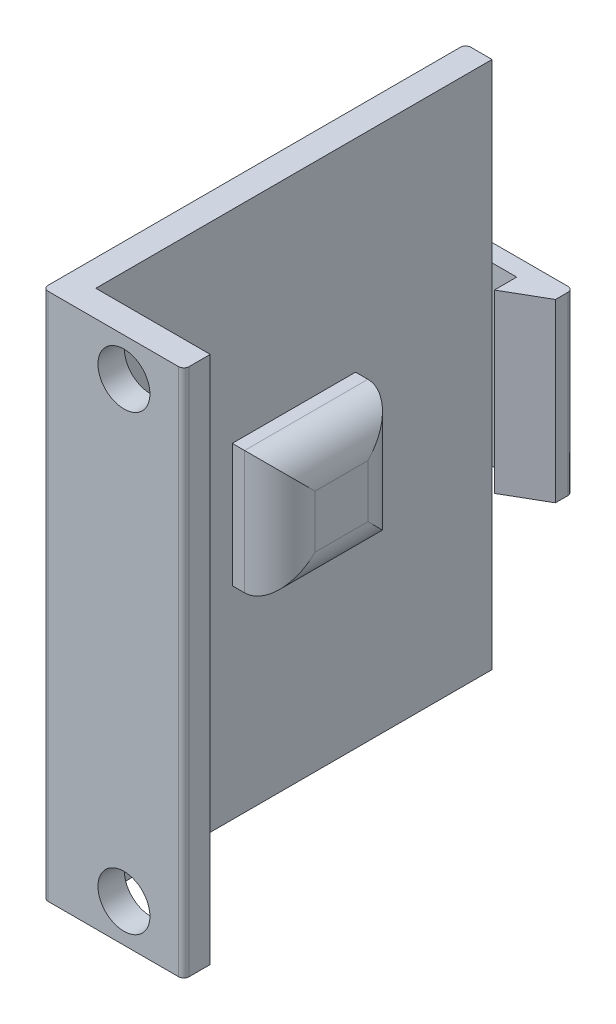
SolidWorks part; units mm, degrees
ref_plane "Front Plane" through (0, 0, 0) normal (0, 0, 1) x (1, 0, 0)
ref_plane "Top Plane" through (0, 0, 0) normal (0, 1, 0) x (1, 0, 0)
ref_plane "Right Plane" through (0, 0, 0) normal (1, 0, 0) x (0, 0, -1)
sketch "Sketch1" plane through (0, 0, 0) normal (0, 1, 0) x (1, 0, 0)
  line L0 (0, 0) -> (-2.2, 0)
  line L5 (-2.2, 0) -> (-2.2, -1.2702)
  line L6 (-2.2, -1.2702) -> (0, 0)
  dimension "D1" = 60
  dimension "D2" = 2.2
extrude "Boss-Extrude1" add sketch "Sketch1" along normal blind 5 and the other way blind 5
sketch "Sketch2" plane through (0, 0, 0) normal (0, 0, -1) x (-1, 0, 0)
  line L0 (0, 5) -> (2.2, 5) construction
  line L1 (0, -5) -> (3.6, -5)
  line L2 (0, -5) -> (0, 5)
  line L3 (0, 5) -> (3.6, 5)
  line L4 (3.6, -5) -> (3.6, 5)
  line L5 (0, -5) -> (3.6, 5) construction
  line L6 (0, 5) -> (3.6, -5) construction
  line L7 (2.2, -5) -> (2.2, 5) construction
  point P4 (1.8, 0)
  dimension "D1" = 1.4
extrude "Boss-Extrude2" add sketch "Sketch2" along normal blind 1
sketch "Sketch3" plane through (-3.6, 0, 0) normal (-1, 0, 0) x (0, 0, 1)
  line L0 (0, 0) -> (12.5427, 0) construction
  line L1 (0, -15) -> (22.5, -15)
  line L2 (0, -15) -> (0, 15)
  line L3 (0, 15) -> (22.5, 15)
  line L4 (22.5, -15) -> (22.5, 15)
  line L5 (0, -15) -> (22.5, 15) construction
  line L6 (0, 15) -> (22.5, -15) construction
  line L7 (0, -5) -> (0, 5) construction
  line L9 (0, 5) -> (-1, 5)
  line L10 (0, 5) -> (0, -5)
  line L11 (0, -5) -> (-1, -5)
  line L12 (-1, 5) -> (-1, -5)
  line L13 (0, 5) -> (-1, -5) construction
  line L14 (0, -5) -> (-1, 5) construction
  point P4 (11.25, 0)
  point P16 (-0.5, 0)
  line M6 (0, -5) -> (0, 5)
  line M7 (0, 5) -> (-1, 5)
  line M8 (-1, 5) -> (-1, -5)
  line M9 (-1, -5) -> (0, -5)
  dimension "D1" = 22.5
  dimension "D2" = 30
extrude "Boss-Extrude3" add sketch "Sketch3" along normal blind 1.5 contours L1 L4 L3 L2 M6 | M9 M6 M7 M8 region at (-3.6, 0, 11.25) region at (-3.6, 0, -0.5)
sketch "Sketch4" plane through (0, 0, 22.5) normal (0, 0, 1) x (1, 0, 0)
  line L0 (-4.35, 0) -> (3.106, 0) construction
  line L1 (-5.1, -15) -> (-3.6, -15)
  line L2 (-5.1, -15) -> (-5.1, 15)
  line L3 (-5.1, 15) -> (-3.6, 15)
  line L4 (-3.6, -15) -> (-3.6, 15)
  line L5 (-5.1, -15) -> (-3.6, 15) construction
  line L6 (-5.1, 15) -> (-3.6, -15) construction
  line L7 (-3.6, -15) -> (2.9, -15)
  line L8 (-3.6, -15) -> (-3.6, 15)
  line L9 (-3.6, 15) -> (2.9, 15)
  line L10 (2.9, -15) -> (2.9, 15)
  line L11 (-3.6, -15) -> (2.9, 15) construction
  line L12 (-3.6, 15) -> (2.9, -15) construction
  circle A0 centre (-0.5, 12.84) radius 1.475
  circle A1 centre (-0.5, -12.84) radius 1.475
  point P4 (-4.35, 0)
  point P11 (-0.35, 0)
  line M5 (-3.6, -15) -> (-3.6, 15)
  line M6 (-3.6, 15) -> (-5.1, 15)
  line M7 (-5.1, 15) -> (-5.1, -15)
  line M8 (-5.1, -15) -> (-3.6, -15)
  dimension "D4" = 2.95
  dimension "D1" = 30
  dimension "D2" = 6.5
  dimension "D3" = 3.4
  dimension "D5" = 2.16
extrude "Boss-Extrude4" add sketch "Sketch4" along normal blind 1.5 contours L7 L10 L9 M5 | M8 M5 M6 M7 region at (-4.35, 0, 22.5) region at (-0.3387, 0, 22.5)
ref_plane "Plane1" through (0, 0, 0) normal (0, 1, 0) x (1, 0, 0)
fillet "Fillet1" radius 0.3 6 edges at (-5.1, 0, -1) (-5.1, 0, 24) (-5.1, -10, 0) (-5.1, 10, 0) (2.9, 0, 24) (0, 0, -1)
sketch "Sketch5" plane through (-3.6, 0, 0) normal (1, 0, 0) x (0, 0, -1)
  line L0 (0, -15) -> (-22.5, -15) construction
  line L1 (0, 15) -> (-22.5, 15)
  line L2 (0, 15) -> (0, -15)
  line L3 (0, -15) -> (-22.5, -15)
  line L4 (-22.5, 15) -> (-22.5, -15)
  line L5 (0, 15) -> (-22.5, -15) construction
  line L6 (0, -15) -> (-22.5, 15) construction
  line L7 (-14.75, 3.5) -> (-7.75, 3.5)
  line L8 (-14.75, 3.5) -> (-14.75, -3.5)
  line L9 (-14.75, -3.5) -> (-7.75, -3.5)
  line L10 (-7.75, 3.5) -> (-7.75, -3.5)
  line L11 (-14.75, 3.5) -> (-7.75, -3.5) construction
  line L12 (-14.75, -3.5) -> (-7.75, 3.5) construction
  line L16 (-22.5, -15) -> (-22.5, 15) construction
  point P4 (-11.25, 0)
  point P7 (-11.25, 0)
  point P12 (0, 0)
  point P13 (0, 0)
  point P14 (-22.4848, -14.1432)
  point P17 (-21.7184, -15)
  dimension "D1" = 7
  dimension "D2" = 7
extrude "Boss-Extrude5" add sketch "Sketch5" along normal blind 2.7 contours L8 L7 L10 L9
fillet "Fillet2" radius 2 4 edges at (-0.9, 0, 14.75) (-0.9, 3.5, 11.25) (-0.9, 0, 7.75) (-0.9, -3.5, 11.25)
